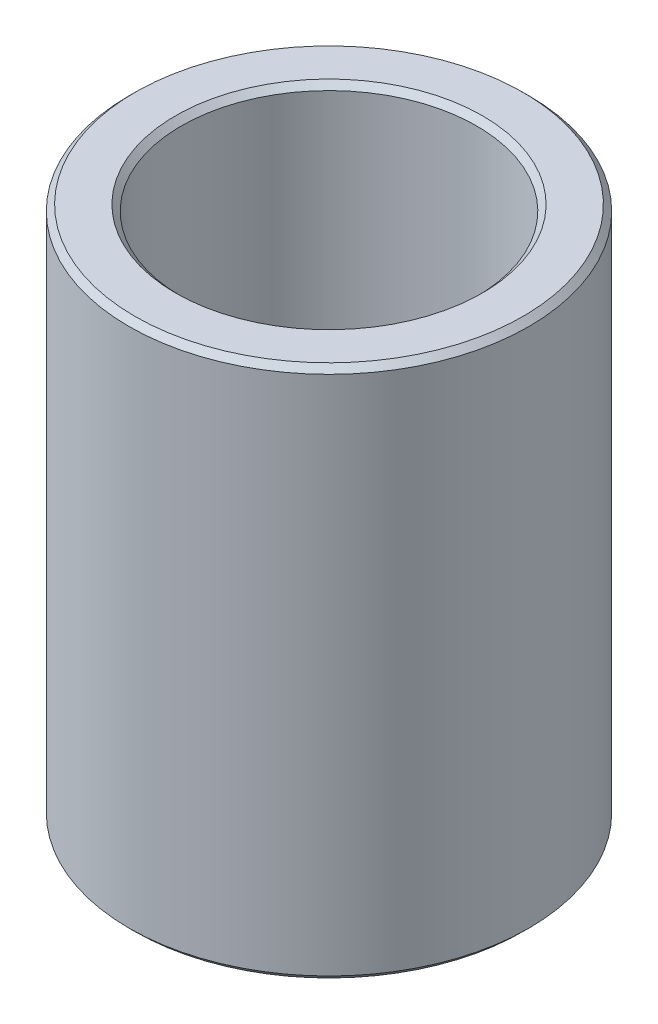
SolidWorks part; units mm, degrees
ref_plane "Front Plane" through (0, 0, 0) normal (0, 0, 1) x (1, 0, 0)
ref_plane "Top Plane" through (0, 0, 0) normal (0, 1, 0) x (1, 0, 0)
ref_plane "Right Plane" through (0, 0, 0) normal (1, 0, 0) x (0, 0, -1)
sketch "Sketch1" plane through (0, 0, 0) normal (0, 1, 0) x (1, 0, 0)
  circle A0 centre (0, 0) radius 52.5
  dimension "SLEEVE_OD" = 105
extrude "Boss-Extrude1" add sketch "Sketch1" along normal blind 139.918
sketch "Sketch2" plane through (0, 0, 0) normal (0, 1, 0) x (1, 0, 0)
  circle A0 centre (0, 0) radius 38.7784
  dimension "BORE_D" = 77.5568
extrude "Cut-Extrude1" cut sketch "Sketch2" along normal through all
chamfer "Chamfer1" distance 1.5392 angle 45 4 edges at (0, 139.918, 38.7784) (0, 0, 38.7784) (0, 0, 52.5) (0, 139.918, 52.5)
